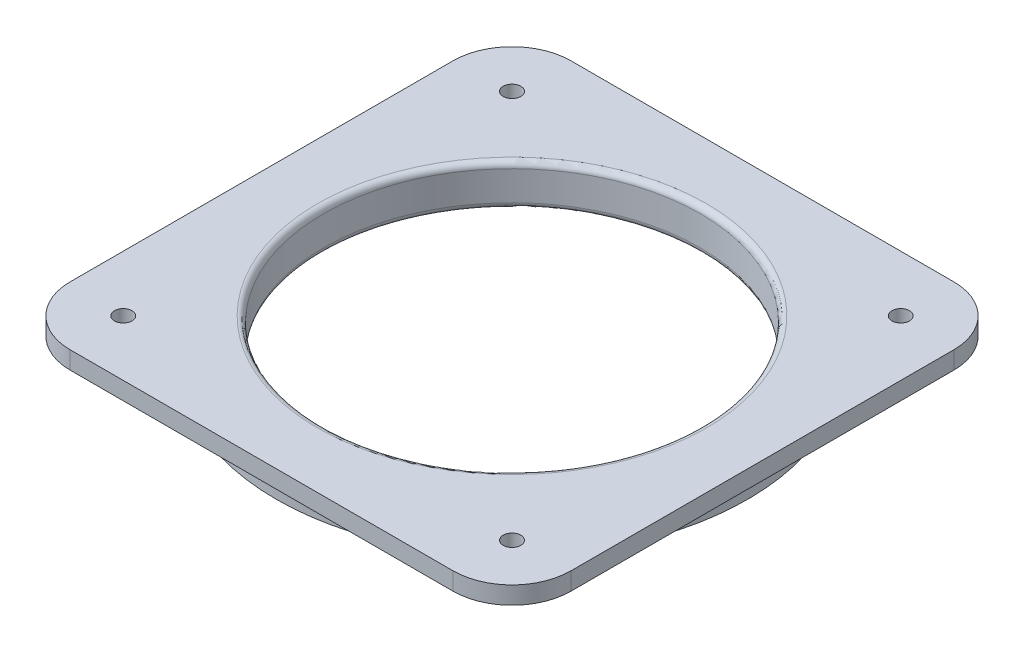
SolidWorks part; units mm, degrees
ref_plane "Plano frontal" through (0, 0, 0) normal (0, 0, 1) x (1, 0, 0)
ref_plane "Plano superior" through (0, 0, 0) normal (0, 1, 0) x (1, 0, 0)
ref_plane "Plano direito" through (0, 0, 0) normal (1, 0, 0) x (0, 0, -1)
ref_plane "Plano1" through (0, -3, 0) normal (0, -1, 0) x (1, 0, 0)
sketch "Esboço1" plane through (0, -3, 0) normal (0, -1, 0) x (1, 0, 0)
  line L0 (-42.5, 42.5) -> (-42.5, -42.5)
  line L1 (-42.5, -42.5) -> (42.5, -42.5)
  line L2 (42.5, -42.5) -> (42.5, 42.5)
  line L3 (42.5, 42.5) -> (-42.5, 42.5)
extrude "Ressalto-extrusão1" add sketch "Esboço1" against normal blind 3
ref_plane "Plano2" through (0, 0, 0) normal (0, 0, -1) x (-1, 0, 0)
sketch "Esboço2" plane through (0, 0, 0) normal (0, 0, -1) x (-1, 0, 0)
  line L0 (-40, -7) -> (0, -7)
  line L1 (0, -7) -> (0, -3)
  line L2 (0, -3) -> (-40, -3)
  line L3 (-40, -3) -> (-40, -7)
  line L4 (0, -7) -> (0, -3) construction
revolve "Revolução1" add sketch "Esboço2" angle 360 about L4 reverse direction yes
hole_wizard "Furo com folga de M521" positions "Esboço4" profile "Esboço3" hole size "M52" standard "Ansi Metric"
sketch "Esboço4" plane through (0, 0, 0) normal (0, 1, 0) x (1, 0, 0)
  point P0 (0, 0)
sketch "Esboço3" plane through (0, 0, 0) normal (1, 0, 0) x (0, 0, 1)
  line L0 (0, 0) -> (0, 7)
  line L1 (0, 7) -> (32, 7)
  line L2 (32, 7) -> (32, 0)
  line L5 (32, 0) -> (0, 0)
  line L11 (0, -6.35) -> (0, 107.95) construction
  dimension "Thru Hole Dia." = 64
  dimension "Thru Hole Depth" = 7
fillet "Filete1" radius 1 2 edges at (0, 0, 32) (0, -7, 32)
fillet "Filete2" radius 10 4 edges at (-42.5, -1.5, 42.5) (42.5, -1.5, 42.5) (-42.5, -1.5, -42.5) (42.5, -1.5, -42.5)
sketch "Esboço5" plane through (0, -3, 0) normal (0, -1, 0) x (1, 0, 0)
  line L0 (33, 0) -> (0, 0) construction
  line L1 (-33, -33) -> (33, -33) construction
  line L2 (-33, -33) -> (-33, 33) construction
  line L3 (-33, 33) -> (33, 33) construction
  line L4 (33, -33) -> (33, 33) construction
  line L5 (-33, -33) -> (33, 33) construction
  line L6 (-33, 33) -> (33, -33) construction
  line L7 (0, 0) -> (0, -33) construction
  circle A0 centre (33, 33) radius 1.5
  circle A1 centre (33, -33) radius 1.5
  circle A2 centre (-33, 33) radius 1.5
  circle A3 centre (-33, -33) radius 1.5
  point P0 (0, 0)
  dimension "D2" = 3
  dimension "D1" = 66
extrude "Corte-extrusão1" cut sketch "Esboço5" against normal blind 10
fillet "Filete3" radius 0.5 4 edges at (-33, -3, 34.5) (-33, -3, -34.5) (33, -3, -31.5) (33, -3, 31.5)
